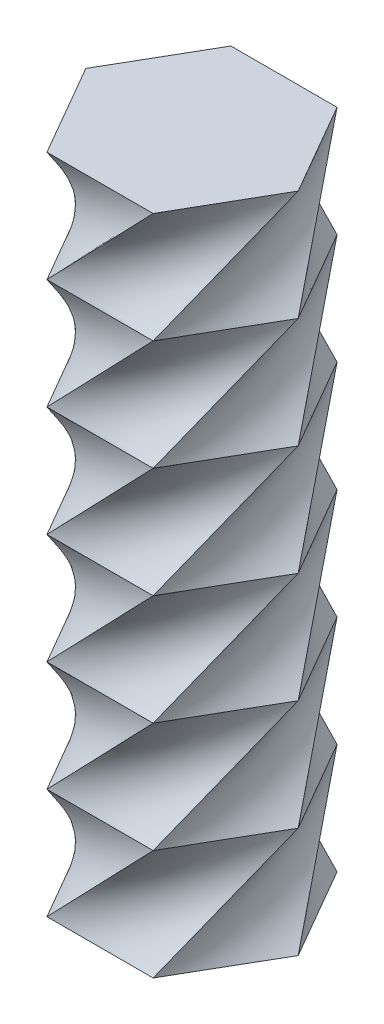
SolidWorks part; units mm, degrees
ref_plane "前视基准面" through (0, 0, 0) normal (0, 0, 1) x (1, 0, 0)
ref_plane "上视基准面" through (0, 0, 0) normal (0, 1, 0) x (1, 0, 0)
ref_plane "右视基准面" through (0, 0, 0) normal (1, 0, 0) x (0, 0, -1)
sketch "草图1" plane through (0, 0, 0) normal (0, 1, 0) x (1, 0, 0)
  line L0 (-28.8675, -50) -> (28.8675, -50)
  line L7 (28.8675, -50) -> (57.735, 0)
  line L8 (57.735, 0) -> (28.8675, 50)
  line L9 (28.8675, 50) -> (-28.8675, 50)
  line L10 (-28.8675, 50) -> (-57.735, 0)
  line L11 (-57.735, 0) -> (-28.8675, -50)
ref_plane "基准面4" through (0, 60, 0) normal (0, 1, 0) x (1, 0, 0)
sketch "草图2" plane through (0, 60, 0) normal (0, 1, 0) x (1, 0, 0)
  line L0 (-28.8675, 50) -> (-57.735, 0) construction
  line L1 (-28.8675, 50) -> (-57.735, 0)
  line L2 (28.8675, 50) -> (-28.8675, 50) construction
  line L4 (57.735, 0) -> (28.8675, 50) construction
  line L6 (28.8675, -50) -> (57.735, 0) construction
  line L8 (-28.8675, -50) -> (28.8675, -50) construction
  line L11 (-57.735, 0) -> (-28.8675, -50) construction
  line L13 (28.8675, 50) -> (-28.8675, 50)
  line L15 (57.735, 0) -> (28.8675, 50)
  line L17 (28.8675, -50) -> (57.735, 0)
  line L19 (-28.8675, -50) -> (28.8675, -50)
  line L22 (-57.735, 0) -> (-28.8675, -50)
loft "放样1" add profiles "草图2", "草图1" connector at (-57.735, 60, 0) connector at (-28.8675, 0, -50)
pattern_linear "阵列(线性)1" count 6 spacing 60 along (0, 1, 0) of "放样1"
